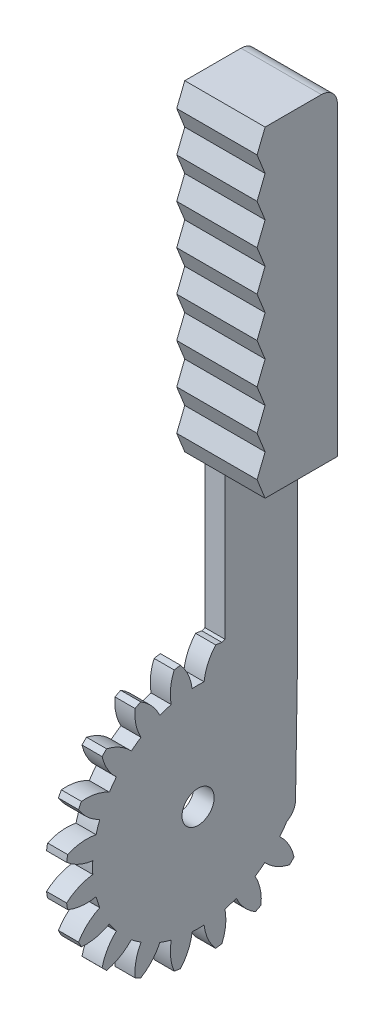
SolidWorks part; units mm, degrees
ref_plane "Plane1" through (0, 0, 0) normal (0, 0, 1) x (1, 0, 0)
ref_plane "Plane2" through (0, 0, 0) normal (0, 1, 0) x (1, 0, 0)
ref_plane "Plane3" through (0, 0, 0) normal (1, 0, 0) x (0, 0, -1)
other "Configuration Table"
sketch "HoldingSke" plane through (0, 0, 0) normal (0, 1, 0) x (1, 0, 0)
  line L0 (0, 0) -> (0.6265, -0.228)
  line L1 (-15, 0) -> (100, 0) construction
  line L2 (0, 0) -> (-2.1039, 2.3779)
  line L3 (0, 0) -> (-11.863, 4.5341)
  line L4 (0, 0) -> (8.1152, 2.9537)
  line L5 (0, 0) -> (-46.8476, -17.4728)
  line L6 (0, 0) -> (-2.0724, -1.3983)
  line L7 (-2.1039, 2.3779) -> (8.6586, 51.2059)
  line L8 (-76.2, 54.61) -> (-75.5, 54.61)
  line L9 (-71.009, 38.7566) -> (-53.1078, 45.2721)
  line L10 (-76.2, 71.12) -> (104.1128, 71.12)
  line L11 (0, 0) -> (-2.5, 0)
  line L12 (-76.2, 101.6) -> (-76.147, 101.6)
  line L13 (24.9733, 27.94) -> (52.9518, 28.4284)
  line L14 (24.9733, 27.94) -> (24.9743, 27.94)
  line L15 (24.9733, 27.94) -> (100.4006, 29.5858)
  line L16 (-63.627, -1.5) -> (-12.827, -1.5)
  circle A0 centre (0, 0) radius 2
  circle A1 centre (0, 0) radius 13.124
  circle A2 centre (0, 0) radius 37.5
  circle A3 centre (0, 0) radius 2
  dimension "Num_teeth" = 20
  dimension "Pitch_radius" = 180.3128
  dimension "Width" = 2.5
  dimension "Thickness" = 2.5
sketch "BasProSke" plane through (0, 0, 0) normal (0, 1, 0) x (1, 0, 0)
  line L0 (-10, 0) -> (60, 0) construction
  line L1 (0, 0) -> (0, 16.5)
  line L2 (0, 0) -> (2.5, 0)
  line L3 (2.5, 0) -> (2.5, 16.5)
  line L4 (2.5, 16.5) -> (0, 16.5)
  dimension "Thickness" = 2.5
  dimension "Diameter" = 33
revolve "Base-Revolve" add sketch "BasProSke" angle 360 about L0
sketch "TooCutSke" plane through (0, 0, 0) normal (1, 0, 0) x (0, 0, -1)
  line L1 (0, 0) -> (0, 107) construction
  line L2 (0, 0) -> (-1.2696, 14.9462) construction
  line L3 (0, 0) -> (-4.6808, 29.5532) construction
  line L4 (-1.2696, 14.9462) -> (-2.3404, 14.7766) construction
  arc A0 (0.7438, 13.1029) -> (-0.7438, 13.1029) centre (0, 0) ccw
  arc A1 (2.21, 16.377) -> (-2.21, 16.377) centre (0, 0) ccw
  circle A2 centre (0, 0) radius 15 construction
  circle A3 centre (0, 0) radius 14.0954 construction
  arc A4 (-0.7438, 13.1029) -> (-2.21, 16.377) centre (-6.7025, 12.3999) ccw
  arc A5 (2.21, 16.377) -> (0.7438, 13.1029) centre (6.7025, 12.3999) ccw
extrude "ToothCut" cut sketch "TooCutSke" along normal through all
fillet "Breaks" [suppressed] radius 0.03 tangent propagation no
fillet "RootFillets" [suppressed] radius 0.376
pattern_circular "TeethCuts" count 20 every 18 about axis through (-10, 0, 0) along (1, 0, 0) of "ToothCut", "RootFillets", "Breaks"
sketch "HubNeaOneSke" plane through (0, 0, 0) normal (-1, 0, 0) x (0, 0, 1)
  circle A0 centre (0, 0) radius 13.124
  dimension "Diameter" = 26.248
extrude "HubNearOne" [suppressed] add sketch "HubNeaOneSke" along normal blind 47.5001
sketch "HubNeaBotSke" plane through (0, 0, 0) normal (-1, 0, 0) x (0, 0, 1)
  circle A0 centre (0, 0) radius 13.124
  dimension "Diameter" = 26.248
extrude "HubNearBoth" [suppressed] add sketch "HubNeaBotSke" along normal blind 23.75
ref_plane "FarPln" through (2.5, 0, 0) normal (1, 0, 0) x (0, 0, -1)
sketch "HubFarSke" plane through (2.5, 0, 0) normal (1, 0, 0) x (0, 0, -1)
  circle A0 centre (0, 0) radius 13.124
  dimension "Diameter" = 26.248
extrude "HubFar" [suppressed] add sketch "HubFarSke" along normal blind 23.75
sketch "BorSke" plane through (0, 0, 0) normal (1, 0, 0) x (0, 0, -1)
  circle A0 centre (0, 0) radius 2
  dimension "Diameter" = 4
extrude "Bore" cut sketch "BorSke" along normal mid plane 100.0001
sketch "KeySke" plane through (0, 0, 0) normal (1, 0, 0) x (0, 0, -1)
  line L0 (-0.8, 0) -> (-0.8, 2.7)
  line L1 (-0.8, 2.7) -> (0.8, 2.7)
  line L2 (0.8, 2.7) -> (0.8, 0)
  line L3 (0, 0) -> (0, 34) construction
  line L4 (-0.8, 0) -> (0.8, 0)
  dimension "Width" = 1.6
extrude "Keyway" [suppressed] cut sketch "KeySke" along normal mid plane 100.0001
pattern_circular "Keyway2" [suppressed] count 2 every 90 about axis through (-10, 0, 0) along (1, 0, 0)
sketch "Sketch1" plane through (2.5, 0, 0) normal (1, 0, 0) x (0, 0, -1)
  line L1 (12.3416, 4.0811) -> (3.3416, 4.0811)
  line L2 (12.3416, 4.0811) -> (12.3416, 74.0811)
  line L3 (12.3416, 74.0811) -> (3.3416, 74.0811)
  line L4 (3.3416, 4.0811) -> (3.3416, 74.0811)
  dimension "D1" = 9
  dimension "D2" = 70
extrude "Boss-Extrude2" add sketch "Sketch1" against normal up to surface (2.5 mm away) up to face at (0, 0, -2)
sketch "Sketch2" plane through (2.5, 0, 0) normal (1, 0, 0) x (0, 0, -1)
  line L3 (3.3416, 74.0811) -> (2.3416, 71.5811)
  line L4 (2.3416, 71.5811) -> (3.3416, 69.0811)
  line L5 (3.3416, 74.0811) -> (3.3416, 15.0369) construction
  line L6 (3.3416, 69.0811) -> (3.3416, 74.0811)
  line L7 (12.3416, 4.4636) -> (12.3416, 4.8084)
  line L8 (12.3416, 7.6405) -> (12.3416, 74.0811)
  line L9 (12.3416, 74.0811) -> (3.3416, 74.0811)
  line L10 (3.3416, 74.0811) -> (3.3416, 15.0369)
  line L11 (12.3416, 4.4636) -> (12.3416, 4.8084)
  line L12 (12.3416, 7.6405) -> (12.3416, 74.0811)
  line L13 (12.3416, 74.0811) -> (3.3416, 74.0811)
  arc A71 (12.6915, 3.3416) -> (12.3416, 4.4636) centre (0, 0) ccw
  arc A72 (12.3416, 4.8084) -> (14.8769, 7.1363) centre (9.7218, 10.2062) ccw
  arc A73 (14.8769, 7.1363) -> (14.5178, 7.8411) centre (0, 0) ccw
  arc A74 (14.5178, 7.8411) -> (12.3416, 7.6405) centre (13.9713, 1.866) ccw
  arc A75 (3.3416, 15.0369) -> (2.9711, 16.2303) centre (-2.5427, 13.8642) ccw
  arc A76 (2.9711, 16.2303) -> (2.1898, 16.354) centre (0, 0) ccw
  arc A77 (2.1898, 16.354) -> (0.7438, 13.1029) centre (6.7025, 12.3999) ccw
  arc A78 (0.7438, 13.1029) -> (-0.7438, 13.1029) centre (0, 0) ccw
  arc A79 (-0.7438, 13.1029) -> (-2.1898, 16.354) centre (-6.7025, 12.3999) ccw
  arc A80 (-2.1898, 16.354) -> (-2.9711, 16.2303) centre (0, 0) ccw
  arc A81 (-2.9711, 16.2303) -> (-3.3416, 12.6915) centre (2.5427, 13.8642) ccw
  arc A82 (-3.3416, 12.6915) -> (-4.7564, 12.2318) centre (0, 0) ccw
  arc A83 (-4.7564, 12.2318) -> (-7.1363, 14.8769) centre (-10.2062, 9.7218) ccw
  arc A84 (-7.1363, 14.8769) -> (-7.8411, 14.5178) centre (0, 0) ccw
  arc A85 (-7.8411, 14.5178) -> (-7.0999, 11.0377) centre (-1.866, 13.9713) ccw
  arc A86 (-7.0999, 11.0377) -> (-8.3035, 10.1633) centre (0, 0) ccw
  arc A87 (-8.3035, 10.1633) -> (-11.3842, 11.9436) centre (-12.7109, 6.0921) ccw
  arc A88 (-11.3842, 11.9436) -> (-11.9436, 11.3842) centre (0, 0) ccw
  arc A89 (-11.9436, 11.3842) -> (-10.1633, 8.3035) centre (-6.0921, 12.7109) ccw
  arc A90 (-10.1633, 8.3035) -> (-11.0377, 7.0999) centre (0, 0) ccw
  arc A91 (-11.0377, 7.0999) -> (-14.5178, 7.8411) centre (-13.9713, 1.866) ccw
  arc A92 (-14.5178, 7.8411) -> (-14.8769, 7.1363) centre (0, 0) ccw
  arc A93 (-14.8769, 7.1363) -> (-12.2318, 4.7564) centre (-9.7218, 10.2062) ccw
  arc A94 (-12.2318, 4.7564) -> (-12.6915, 3.3416) centre (0, 0) ccw
  arc A95 (-12.6915, 3.3416) -> (-16.2303, 2.9711) centre (-13.8642, -2.5427) ccw
  arc A96 (-16.2303, 2.9711) -> (-16.354, 2.1898) centre (0, 0) ccw
  arc A97 (-16.354, 2.1898) -> (-13.1029, 0.7438) centre (-12.3999, 6.7025) ccw
  arc A98 (-13.1029, 0.7438) -> (-13.1029, -0.7438) centre (0, 0) ccw
  arc A99 (-13.1029, -0.7438) -> (-16.354, -2.1898) centre (-12.3999, -6.7025) ccw
  arc A100 (-16.354, -2.1898) -> (-16.2303, -2.9711) centre (0, 0) ccw
  arc A101 (-16.2303, -2.9711) -> (-12.6915, -3.3416) centre (-13.8642, 2.5427) ccw
  arc A102 (-12.6915, -3.3416) -> (-12.2318, -4.7564) centre (0, 0) ccw
  arc A103 (-12.2318, -4.7564) -> (-14.8769, -7.1363) centre (-9.7218, -10.2062) ccw
  arc A104 (-14.8769, -7.1363) -> (-14.5178, -7.8411) centre (0, 0) ccw
  arc A105 (-14.5178, -7.8411) -> (-11.0377, -7.0999) centre (-13.9713, -1.866) ccw
  arc A106 (-11.0377, -7.0999) -> (-10.1633, -8.3035) centre (0, 0) ccw
  arc A107 (-10.1633, -8.3035) -> (-11.9436, -11.3842) centre (-6.0921, -12.7109) ccw
  arc A108 (-11.9436, -11.3842) -> (-11.3842, -11.9436) centre (0, 0) ccw
  arc A109 (-11.3842, -11.9436) -> (-8.3035, -10.1633) centre (-12.7109, -6.0921) ccw
  arc A110 (-8.3035, -10.1633) -> (-7.0999, -11.0377) centre (0, 0) ccw
  arc A111 (-7.0999, -11.0377) -> (-7.8411, -14.5178) centre (-1.866, -13.9713) ccw
  arc A112 (-7.8411, -14.5178) -> (-7.1363, -14.8769) centre (0, 0) ccw
  arc A113 (-7.1363, -14.8769) -> (-4.7564, -12.2318) centre (-10.2062, -9.7218) ccw
  arc A114 (-4.7564, -12.2318) -> (-3.3416, -12.6915) centre (0, 0) ccw
  arc A115 (-3.3416, -12.6915) -> (-2.9711, -16.2303) centre (2.5427, -13.8642) ccw
  arc A116 (-2.9711, -16.2303) -> (-2.1898, -16.354) centre (0, 0) ccw
  arc A117 (-2.1898, -16.354) -> (-0.7438, -13.1029) centre (-6.7025, -12.3999) ccw
  arc A118 (-0.7438, -13.1029) -> (0.7438, -13.1029) centre (0, 0) ccw
  arc A119 (0.7438, -13.1029) -> (2.1898, -16.354) centre (6.7025, -12.3999) ccw
  arc A120 (2.1898, -16.354) -> (2.9711, -16.2303) centre (0, 0) ccw
  arc A121 (2.9711, -16.2303) -> (3.3416, -12.6915) centre (-2.5427, -13.8642) ccw
  arc A122 (3.3416, -12.6915) -> (4.7564, -12.2318) centre (0, 0) ccw
  arc A123 (4.7564, -12.2318) -> (7.1363, -14.8769) centre (10.2062, -9.7218) ccw
  arc A124 (7.1363, -14.8769) -> (7.8411, -14.5178) centre (0, 0) ccw
  arc A125 (7.8411, -14.5178) -> (7.0999, -11.0377) centre (1.866, -13.9713) ccw
  arc A126 (7.0999, -11.0377) -> (8.3035, -10.1633) centre (0, 0) ccw
  arc A127 (8.3035, -10.1633) -> (11.3842, -11.9436) centre (12.7109, -6.0921) ccw
  arc A128 (11.3842, -11.9436) -> (11.9436, -11.3842) centre (0, 0) ccw
  arc A129 (11.9436, -11.3842) -> (10.1633, -8.3035) centre (6.0921, -12.7109) ccw
  arc A130 (10.1633, -8.3035) -> (11.0377, -7.0999) centre (0, 0) ccw
  arc A131 (11.0377, -7.0999) -> (14.5178, -7.8411) centre (13.9713, -1.866) ccw
  arc A132 (14.5178, -7.8411) -> (14.8769, -7.1363) centre (0, 0) ccw
  arc A133 (14.8769, -7.1363) -> (12.2318, -4.7564) centre (9.7218, -10.2062) ccw
  arc A134 (12.2318, -4.7564) -> (12.6915, -3.3416) centre (0, 0) ccw
  arc A135 (12.6915, -3.3416) -> (16.2303, -2.9711) centre (13.8642, 2.5427) ccw
  arc A136 (16.2303, -2.9711) -> (16.354, -2.1898) centre (0, 0) ccw
  arc A137 (16.354, -2.1898) -> (13.1029, -0.7438) centre (12.3999, -6.7025) ccw
  arc A138 (13.1029, -0.7438) -> (13.1029, 0.7438) centre (0, 0) ccw
  arc A139 (13.1029, 0.7438) -> (16.354, 2.1898) centre (12.3999, 6.7025) ccw
  arc A140 (16.354, 2.1898) -> (16.2303, 2.9711) centre (0, 0) ccw
  arc A141 (16.2303, 2.9711) -> (12.6915, 3.3416) centre (13.8642, -2.5427) ccw
  arc A142 (12.6915, 3.3416) -> (12.3416, 4.4636) centre (0, 0) ccw
  arc A143 (12.3416, 4.8084) -> (14.8769, 7.1363) centre (9.7218, 10.2062) ccw
  arc A144 (14.8769, 7.1363) -> (14.5178, 7.8411) centre (0, 0) ccw
  arc A145 (14.5178, 7.8411) -> (12.3416, 7.6405) centre (13.9713, 1.866) ccw
  arc A146 (3.3416, 15.0369) -> (2.9711, 16.2303) centre (-2.5427, 13.8642) ccw
  arc A147 (2.9711, 16.2303) -> (2.1898, 16.354) centre (0, 0) ccw
  arc A148 (2.1898, 16.354) -> (0.7438, 13.1029) centre (6.7025, 12.3999) ccw
  arc A149 (0.7438, 13.1029) -> (-0.7438, 13.1029) centre (0, 0) ccw
  arc A150 (-0.7438, 13.1029) -> (-2.1898, 16.354) centre (-6.7025, 12.3999) ccw
  arc A151 (-2.1898, 16.354) -> (-2.9711, 16.2303) centre (0, 0) ccw
  arc A152 (-2.9711, 16.2303) -> (-3.3416, 12.6915) centre (2.5427, 13.8642) ccw
  arc A153 (-3.3416, 12.6915) -> (-4.7564, 12.2318) centre (0, 0) ccw
  arc A154 (-4.7564, 12.2318) -> (-7.1363, 14.8769) centre (-10.2062, 9.7218) ccw
  arc A155 (-7.1363, 14.8769) -> (-7.8411, 14.5178) centre (0, 0) ccw
  arc A156 (-7.8411, 14.5178) -> (-7.0999, 11.0377) centre (-1.866, 13.9713) ccw
  arc A157 (-7.0999, 11.0377) -> (-8.3035, 10.1633) centre (0, 0) ccw
  arc A158 (-8.3035, 10.1633) -> (-11.3842, 11.9436) centre (-12.7109, 6.0921) ccw
  arc A159 (-11.3842, 11.9436) -> (-11.9436, 11.3842) centre (0, 0) ccw
  arc A160 (-11.9436, 11.3842) -> (-10.1633, 8.3035) centre (-6.0921, 12.7109) ccw
  arc A161 (-10.1633, 8.3035) -> (-11.0377, 7.0999) centre (0, 0) ccw
  arc A162 (-11.0377, 7.0999) -> (-14.5178, 7.8411) centre (-13.9713, 1.866) ccw
  arc A163 (-14.5178, 7.8411) -> (-14.8769, 7.1363) centre (0, 0) ccw
  arc A164 (-14.8769, 7.1363) -> (-12.2318, 4.7564) centre (-9.7218, 10.2062) ccw
  arc A165 (-12.2318, 4.7564) -> (-12.6915, 3.3416) centre (0, 0) ccw
  arc A166 (-12.6915, 3.3416) -> (-16.2303, 2.9711) centre (-13.8642, -2.5427) ccw
  arc A167 (-16.2303, 2.9711) -> (-16.354, 2.1898) centre (0, 0) ccw
  arc A168 (-16.354, 2.1898) -> (-13.1029, 0.7438) centre (-12.3999, 6.7025) ccw
  arc A169 (-13.1029, 0.7438) -> (-13.1029, -0.7438) centre (0, 0) ccw
  arc A170 (-13.1029, -0.7438) -> (-16.354, -2.1898) centre (-12.3999, -6.7025) ccw
  arc A171 (-16.354, -2.1898) -> (-16.2303, -2.9711) centre (0, 0) ccw
  arc A172 (-16.2303, -2.9711) -> (-12.6915, -3.3416) centre (-13.8642, 2.5427) ccw
  arc A173 (-12.6915, -3.3416) -> (-12.2318, -4.7564) centre (0, 0) ccw
  arc A174 (-12.2318, -4.7564) -> (-14.8769, -7.1363) centre (-9.7218, -10.2062) ccw
  arc A175 (-14.8769, -7.1363) -> (-14.5178, -7.8411) centre (0, 0) ccw
  arc A176 (-14.5178, -7.8411) -> (-11.0377, -7.0999) centre (-13.9713, -1.866) ccw
  arc A177 (-11.0377, -7.0999) -> (-10.1633, -8.3035) centre (0, 0) ccw
  arc A178 (-10.1633, -8.3035) -> (-11.9436, -11.3842) centre (-6.0921, -12.7109) ccw
  arc A179 (-11.9436, -11.3842) -> (-11.3842, -11.9436) centre (0, 0) ccw
  arc A180 (-11.3842, -11.9436) -> (-8.3035, -10.1633) centre (-12.7109, -6.0921) ccw
  arc A181 (-8.3035, -10.1633) -> (-7.0999, -11.0377) centre (0, 0) ccw
  arc A182 (-7.0999, -11.0377) -> (-7.8411, -14.5178) centre (-1.866, -13.9713) ccw
  arc A183 (-7.8411, -14.5178) -> (-7.1363, -14.8769) centre (0, 0) ccw
  arc A184 (-7.1363, -14.8769) -> (-4.7564, -12.2318) centre (-10.2062, -9.7218) ccw
  arc A185 (-4.7564, -12.2318) -> (-3.3416, -12.6915) centre (0, 0) ccw
  arc A186 (-3.3416, -12.6915) -> (-2.9711, -16.2303) centre (2.5427, -13.8642) ccw
  arc A187 (-2.9711, -16.2303) -> (-2.1898, -16.354) centre (0, 0) ccw
  arc A188 (-2.1898, -16.354) -> (-0.7438, -13.1029) centre (-6.7025, -12.3999) ccw
  arc A189 (-0.7438, -13.1029) -> (0.7438, -13.1029) centre (0, 0) ccw
  arc A190 (0.7438, -13.1029) -> (2.1898, -16.354) centre (6.7025, -12.3999) ccw
  arc A191 (2.1898, -16.354) -> (2.9711, -16.2303) centre (0, 0) ccw
  arc A192 (2.9711, -16.2303) -> (3.3416, -12.6915) centre (-2.5427, -13.8642) ccw
  arc A193 (3.3416, -12.6915) -> (4.7564, -12.2318) centre (0, 0) ccw
  arc A194 (4.7564, -12.2318) -> (7.1363, -14.8769) centre (10.2062, -9.7218) ccw
  arc A195 (7.1363, -14.8769) -> (7.8411, -14.5178) centre (0, 0) ccw
  arc A196 (7.8411, -14.5178) -> (7.0999, -11.0377) centre (1.866, -13.9713) ccw
  arc A197 (7.0999, -11.0377) -> (8.3035, -10.1633) centre (0, 0) ccw
  arc A198 (8.3035, -10.1633) -> (11.3842, -11.9436) centre (12.7109, -6.0921) ccw
  arc A199 (11.3842, -11.9436) -> (11.9436, -11.3842) centre (0, 0) ccw
  arc A200 (11.9436, -11.3842) -> (10.1633, -8.3035) centre (6.0921, -12.7109) ccw
  arc A201 (10.1633, -8.3035) -> (11.0377, -7.0999) centre (0, 0) ccw
  arc A202 (11.0377, -7.0999) -> (14.5178, -7.8411) centre (13.9713, -1.866) ccw
  arc A203 (14.5178, -7.8411) -> (14.8769, -7.1363) centre (0, 0) ccw
  arc A204 (14.8769, -7.1363) -> (12.2318, -4.7564) centre (9.7218, -10.2062) ccw
  arc A205 (12.2318, -4.7564) -> (12.6915, -3.3416) centre (0, 0) ccw
  arc A206 (12.6915, -3.3416) -> (16.2303, -2.9711) centre (13.8642, 2.5427) ccw
  arc A207 (16.2303, -2.9711) -> (16.354, -2.1898) centre (0, 0) ccw
  arc A208 (16.354, -2.1898) -> (13.1029, -0.7438) centre (12.3999, -6.7025) ccw
  arc A209 (13.1029, -0.7438) -> (13.1029, 0.7438) centre (0, 0) ccw
  arc A210 (13.1029, 0.7438) -> (16.354, 2.1898) centre (12.3999, 6.7025) ccw
  arc A211 (16.354, 2.1898) -> (16.2303, 2.9711) centre (0, 0) ccw
  arc A212 (16.2303, 2.9711) -> (12.6915, 3.3416) centre (13.8642, -2.5427) ccw
  dimension "D1" = 5
  dimension "D2" = 1
  dimension "D3" = 0
extrude "Boss-Extrude3" add sketch "Sketch2" against normal up to surface (2.5 mm away) contours L4 L6 L3 region at (2.5, 71.5811, -3.0083) up to face at (0, 0.8087, 0.528)
pattern_linear "LPattern2" count 8 spacing 5 along (0, -1, 0) of "Boss-Extrude3"
sketch "Sketch3" plane through (2.5, 0, 0) normal (1, 0, 0) x (0, 0, -1)
  line L0 (12.3416, 7.6405) -> (11.9436, -16.474)
  line L1 (11.9436, -16.474) -> (28.1206, -19.0025)
  line L2 (28.1206, -19.0025) -> (23.7943, 10.9484)
  line L3 (23.7943, 10.9484) -> (12.3416, 7.6405)
extrude "Cut-Extrude1" cut sketch "Sketch3" against normal blind 3
fillet "Fillet3" radius 2 1 edges at (1.25, -7.5637, -12.0907)
fillet "Fillet4" radius 2 1 edges at (1.25, 74.0811, -12.3416)
sketch "Sketch5" plane through (2.5, 0, 0) normal (1, 0, 0) x (0, 0, -1)
  line L0 (2.9711, 16.2303) -> (3.3416, 16.3893)
  line L1 (3.3416, 16.3893) -> (3.3416, 15.0369)
  line L2 (2.9711, 16.2303) -> (3.3416, 15.0369)
  line L20 (12.3416, 7.6405) -> (12.3416, 72.0811)
  line L21 (10.3416, 74.0811) -> (3.3416, 74.0811)
  line L22 (3.3416, 74.0811) -> (2.3416, 71.5811)
  line L23 (2.3416, 71.5811) -> (3.3416, 69.0811)
  line L24 (3.3416, 69.0811) -> (2.3416, 66.5811)
  line L25 (2.3416, 66.5811) -> (3.3416, 64.0811)
  line L26 (3.3416, 64.0811) -> (2.3416, 61.5811)
  line L27 (2.3416, 61.5811) -> (3.3416, 59.0811)
  line L28 (3.3416, 59.0811) -> (2.3416, 56.5811)
  line L29 (2.3416, 56.5811) -> (3.3416, 54.0811)
  line L30 (3.3416, 54.0811) -> (2.3416, 51.5811)
  line L31 (2.3416, 51.5811) -> (3.3416, 49.0811)
  line L32 (3.3416, 49.0811) -> (2.3416, 46.5811)
  line L33 (2.3416, 46.5811) -> (3.3416, 44.0811)
  line L34 (3.3416, 44.0811) -> (2.3416, 41.5811)
  line L35 (2.3416, 41.5811) -> (3.3416, 39.0811)
  line L36 (3.3416, 39.0811) -> (2.3416, 36.5811)
  line L37 (2.3416, 36.5811) -> (3.3416, 34.0811)
  line L38 (3.3416, 34.0811) -> (3.3416, 15.0369)
  line L39 (12.1272, -5.3521) -> (12.3416, 7.6405)
  line L40 (12.3416, 7.6405) -> (12.3416, 72.0811)
  line L41 (10.3416, 74.0811) -> (3.3416, 74.0811)
  line L42 (3.3416, 74.0811) -> (2.3416, 71.5811)
  line L43 (2.3416, 71.5811) -> (3.3416, 69.0811)
  line L44 (3.3416, 69.0811) -> (2.3416, 66.5811)
  line L45 (2.3416, 66.5811) -> (3.3416, 64.0811)
  line L46 (3.3416, 64.0811) -> (2.3416, 61.5811)
  line L47 (2.3416, 61.5811) -> (3.3416, 59.0811)
  line L48 (3.3416, 59.0811) -> (2.3416, 56.5811)
  line L49 (2.3416, 56.5811) -> (3.3416, 54.0811)
  line L50 (3.3416, 54.0811) -> (2.3416, 51.5811)
  line L51 (2.3416, 51.5811) -> (3.3416, 49.0811)
  line L52 (3.3416, 49.0811) -> (2.3416, 46.5811)
  line L53 (2.3416, 46.5811) -> (3.3416, 44.0811)
  line L54 (3.3416, 44.0811) -> (2.3416, 41.5811)
  line L55 (2.3416, 41.5811) -> (3.3416, 39.0811)
  line L56 (3.3416, 39.0811) -> (2.3416, 36.5811)
  line L57 (2.3416, 36.5811) -> (3.3416, 34.0811)
  line L58 (3.3416, 34.0811) -> (3.3416, 15.0369)
  line L59 (12.1272, -5.3521) -> (12.3416, 7.6405)
  arc A58 (12.3416, 72.0811) -> (10.3416, 74.0811) centre (10.3416, 72.0811) ccw
  arc A59 (3.3416, 15.0369) -> (2.9711, 16.2303) centre (-2.5427, 13.8642) ccw
  arc A60 (2.9711, 16.2303) -> (2.1898, 16.354) centre (0, 0) ccw
  arc A61 (2.1898, 16.354) -> (0.7438, 13.1029) centre (6.7025, 12.3999) ccw
  arc A62 (0.7438, 13.1029) -> (-0.7438, 13.1029) centre (0, 0) ccw
  arc A63 (-0.7438, 13.1029) -> (-2.1898, 16.354) centre (-6.7025, 12.3999) ccw
  arc A64 (-2.1898, 16.354) -> (-2.9711, 16.2303) centre (0, 0) ccw
  arc A65 (-2.9711, 16.2303) -> (-3.3416, 12.6915) centre (2.5427, 13.8642) ccw
  arc A66 (-3.3416, 12.6915) -> (-4.7564, 12.2318) centre (0, 0) ccw
  arc A67 (-4.7564, 12.2318) -> (-7.1363, 14.8769) centre (-10.2062, 9.7218) ccw
  arc A68 (-7.1363, 14.8769) -> (-7.8411, 14.5178) centre (0, 0) ccw
  arc A69 (-7.8411, 14.5178) -> (-7.0999, 11.0377) centre (-1.866, 13.9713) ccw
  arc A70 (-7.0999, 11.0377) -> (-8.3035, 10.1633) centre (0, 0) ccw
  arc A71 (-8.3035, 10.1633) -> (-11.3842, 11.9436) centre (-12.7109, 6.0921) ccw
  arc A72 (-11.3842, 11.9436) -> (-11.9436, 11.3842) centre (0, 0) ccw
  arc A73 (-11.9436, 11.3842) -> (-10.1633, 8.3035) centre (-6.0921, 12.7109) ccw
  arc A74 (-10.1633, 8.3035) -> (-11.0377, 7.0999) centre (0, 0) ccw
  arc A75 (-11.0377, 7.0999) -> (-14.5178, 7.8411) centre (-13.9713, 1.866) ccw
  arc A76 (-14.5178, 7.8411) -> (-14.8769, 7.1363) centre (0, 0) ccw
  arc A77 (-14.8769, 7.1363) -> (-12.2318, 4.7564) centre (-9.7218, 10.2062) ccw
  arc A78 (-12.2318, 4.7564) -> (-12.6915, 3.3416) centre (0, 0) ccw
  arc A79 (-12.6915, 3.3416) -> (-16.2303, 2.9711) centre (-13.8642, -2.5427) ccw
  arc A80 (-16.2303, 2.9711) -> (-16.354, 2.1898) centre (0, 0) ccw
  arc A81 (-16.354, 2.1898) -> (-13.1029, 0.7438) centre (-12.3999, 6.7025) ccw
  arc A82 (-13.1029, 0.7438) -> (-13.1029, -0.7438) centre (0, 0) ccw
  arc A83 (-13.1029, -0.7438) -> (-16.354, -2.1898) centre (-12.3999, -6.7025) ccw
  arc A84 (-16.354, -2.1898) -> (-16.2303, -2.9711) centre (0, 0) ccw
  arc A85 (-16.2303, -2.9711) -> (-12.6915, -3.3416) centre (-13.8642, 2.5427) ccw
  arc A86 (-12.6915, -3.3416) -> (-12.2318, -4.7564) centre (0, 0) ccw
  arc A87 (-12.2318, -4.7564) -> (-14.8769, -7.1363) centre (-9.7218, -10.2062) ccw
  arc A88 (-14.8769, -7.1363) -> (-14.5178, -7.8411) centre (0, 0) ccw
  arc A89 (-14.5178, -7.8411) -> (-11.0377, -7.0999) centre (-13.9713, -1.866) ccw
  arc A90 (-11.0377, -7.0999) -> (-10.1633, -8.3035) centre (0, 0) ccw
  arc A91 (-10.1633, -8.3035) -> (-11.9436, -11.3842) centre (-6.0921, -12.7109) ccw
  arc A92 (-11.9436, -11.3842) -> (-11.3842, -11.9436) centre (0, 0) ccw
  arc A93 (-11.3842, -11.9436) -> (-8.3035, -10.1633) centre (-12.7109, -6.0921) ccw
  arc A94 (-8.3035, -10.1633) -> (-7.0999, -11.0377) centre (0, 0) ccw
  arc A95 (-7.0999, -11.0377) -> (-7.8411, -14.5178) centre (-1.866, -13.9713) ccw
  arc A96 (-7.8411, -14.5178) -> (-7.1363, -14.8769) centre (0, 0) ccw
  arc A97 (-7.1363, -14.8769) -> (-4.7564, -12.2318) centre (-10.2062, -9.7218) ccw
  arc A98 (-4.7564, -12.2318) -> (-3.3416, -12.6915) centre (0, 0) ccw
  arc A99 (-3.3416, -12.6915) -> (-2.9711, -16.2303) centre (2.5427, -13.8642) ccw
  arc A100 (-2.9711, -16.2303) -> (-2.1898, -16.354) centre (0, 0) ccw
  arc A101 (-2.1898, -16.354) -> (-0.7438, -13.1029) centre (-6.7025, -12.3999) ccw
  arc A102 (-0.7438, -13.1029) -> (0.7438, -13.1029) centre (0, 0) ccw
  arc A103 (0.7438, -13.1029) -> (2.1898, -16.354) centre (6.7025, -12.3999) ccw
  arc A104 (2.1898, -16.354) -> (2.9711, -16.2303) centre (0, 0) ccw
  arc A105 (2.9711, -16.2303) -> (3.3416, -12.6915) centre (-2.5427, -13.8642) ccw
  arc A106 (3.3416, -12.6915) -> (4.7564, -12.2318) centre (0, 0) ccw
  arc A107 (4.7564, -12.2318) -> (7.1363, -14.8769) centre (10.2062, -9.7218) ccw
  arc A108 (7.1363, -14.8769) -> (7.8411, -14.5178) centre (0, 0) ccw
  arc A109 (7.8411, -14.5178) -> (7.0999, -11.0377) centre (1.866, -13.9713) ccw
  arc A110 (7.0999, -11.0377) -> (8.3035, -10.1633) centre (0, 0) ccw
  arc A111 (8.3035, -10.1633) -> (11.3842, -11.9436) centre (12.7109, -6.0921) ccw
  arc A112 (11.3842, -11.9436) -> (11.9436, -11.3842) centre (0, 0) ccw
  arc A113 (11.9436, -11.3842) -> (10.1633, -8.3035) centre (6.0921, -12.7109) ccw
  arc A114 (10.1633, -8.3035) -> (11.0377, -7.0999) centre (0, 0) ccw
  arc A115 (11.0377, -7.0999) -> (12.1272, -5.3521) centre (10.1274, -5.3191) ccw
  arc A116 (12.3416, 72.0811) -> (10.3416, 74.0811) centre (10.3416, 72.0811) ccw
  arc A117 (3.3416, 15.0369) -> (2.9711, 16.2303) centre (-2.5427, 13.8642) ccw
  arc A118 (2.9711, 16.2303) -> (2.1898, 16.354) centre (0, 0) ccw
  arc A119 (2.1898, 16.354) -> (0.7438, 13.1029) centre (6.7025, 12.3999) ccw
  arc A120 (0.7438, 13.1029) -> (-0.7438, 13.1029) centre (0, 0) ccw
  arc A121 (-0.7438, 13.1029) -> (-2.1898, 16.354) centre (-6.7025, 12.3999) ccw
  arc A122 (-2.1898, 16.354) -> (-2.9711, 16.2303) centre (0, 0) ccw
  arc A123 (-2.9711, 16.2303) -> (-3.3416, 12.6915) centre (2.5427, 13.8642) ccw
  arc A124 (-3.3416, 12.6915) -> (-4.7564, 12.2318) centre (0, 0) ccw
  arc A125 (-4.7564, 12.2318) -> (-7.1363, 14.8769) centre (-10.2062, 9.7218) ccw
  arc A126 (-7.1363, 14.8769) -> (-7.8411, 14.5178) centre (0, 0) ccw
  arc A127 (-7.8411, 14.5178) -> (-7.0999, 11.0377) centre (-1.866, 13.9713) ccw
  arc A128 (-7.0999, 11.0377) -> (-8.3035, 10.1633) centre (0, 0) ccw
  arc A129 (-8.3035, 10.1633) -> (-11.3842, 11.9436) centre (-12.7109, 6.0921) ccw
  arc A130 (-11.3842, 11.9436) -> (-11.9436, 11.3842) centre (0, 0) ccw
  arc A131 (-11.9436, 11.3842) -> (-10.1633, 8.3035) centre (-6.0921, 12.7109) ccw
  arc A132 (-10.1633, 8.3035) -> (-11.0377, 7.0999) centre (0, 0) ccw
  arc A133 (-11.0377, 7.0999) -> (-14.5178, 7.8411) centre (-13.9713, 1.866) ccw
  arc A134 (-14.5178, 7.8411) -> (-14.8769, 7.1363) centre (0, 0) ccw
  arc A135 (-14.8769, 7.1363) -> (-12.2318, 4.7564) centre (-9.7218, 10.2062) ccw
  arc A136 (-12.2318, 4.7564) -> (-12.6915, 3.3416) centre (0, 0) ccw
  arc A137 (-12.6915, 3.3416) -> (-16.2303, 2.9711) centre (-13.8642, -2.5427) ccw
  arc A138 (-16.2303, 2.9711) -> (-16.354, 2.1898) centre (0, 0) ccw
  arc A139 (-16.354, 2.1898) -> (-13.1029, 0.7438) centre (-12.3999, 6.7025) ccw
  arc A140 (-13.1029, 0.7438) -> (-13.1029, -0.7438) centre (0, 0) ccw
  arc A141 (-13.1029, -0.7438) -> (-16.354, -2.1898) centre (-12.3999, -6.7025) ccw
  arc A142 (-16.354, -2.1898) -> (-16.2303, -2.9711) centre (0, 0) ccw
  arc A143 (-16.2303, -2.9711) -> (-12.6915, -3.3416) centre (-13.8642, 2.5427) ccw
  arc A144 (-12.6915, -3.3416) -> (-12.2318, -4.7564) centre (0, 0) ccw
  arc A145 (-12.2318, -4.7564) -> (-14.8769, -7.1363) centre (-9.7218, -10.2062) ccw
  arc A146 (-14.8769, -7.1363) -> (-14.5178, -7.8411) centre (0, 0) ccw
  arc A147 (-14.5178, -7.8411) -> (-11.0377, -7.0999) centre (-13.9713, -1.866) ccw
  arc A148 (-11.0377, -7.0999) -> (-10.1633, -8.3035) centre (0, 0) ccw
  arc A149 (-10.1633, -8.3035) -> (-11.9436, -11.3842) centre (-6.0921, -12.7109) ccw
  arc A150 (-11.9436, -11.3842) -> (-11.3842, -11.9436) centre (0, 0) ccw
  arc A151 (-11.3842, -11.9436) -> (-8.3035, -10.1633) centre (-12.7109, -6.0921) ccw
  arc A152 (-8.3035, -10.1633) -> (-7.0999, -11.0377) centre (0, 0) ccw
  arc A153 (-7.0999, -11.0377) -> (-7.8411, -14.5178) centre (-1.866, -13.9713) ccw
  arc A154 (-7.8411, -14.5178) -> (-7.1363, -14.8769) centre (0, 0) ccw
  arc A155 (-7.1363, -14.8769) -> (-4.7564, -12.2318) centre (-10.2062, -9.7218) ccw
  arc A156 (-4.7564, -12.2318) -> (-3.3416, -12.6915) centre (0, 0) ccw
  arc A157 (-3.3416, -12.6915) -> (-2.9711, -16.2303) centre (2.5427, -13.8642) ccw
  arc A158 (-2.9711, -16.2303) -> (-2.1898, -16.354) centre (0, 0) ccw
  arc A159 (-2.1898, -16.354) -> (-0.7438, -13.1029) centre (-6.7025, -12.3999) ccw
  arc A160 (-0.7438, -13.1029) -> (0.7438, -13.1029) centre (0, 0) ccw
  arc A161 (0.7438, -13.1029) -> (2.1898, -16.354) centre (6.7025, -12.3999) ccw
  arc A162 (2.1898, -16.354) -> (2.9711, -16.2303) centre (0, 0) ccw
  arc A163 (2.9711, -16.2303) -> (3.3416, -12.6915) centre (-2.5427, -13.8642) ccw
  arc A164 (3.3416, -12.6915) -> (4.7564, -12.2318) centre (0, 0) ccw
  arc A165 (4.7564, -12.2318) -> (7.1363, -14.8769) centre (10.2062, -9.7218) ccw
  arc A166 (7.1363, -14.8769) -> (7.8411, -14.5178) centre (0, 0) ccw
  arc A167 (7.8411, -14.5178) -> (7.0999, -11.0377) centre (1.866, -13.9713) ccw
  arc A168 (7.0999, -11.0377) -> (8.3035, -10.1633) centre (0, 0) ccw
  arc A169 (8.3035, -10.1633) -> (11.3842, -11.9436) centre (12.7109, -6.0921) ccw
  arc A170 (11.3842, -11.9436) -> (11.9436, -11.3842) centre (0, 0) ccw
  arc A171 (11.9436, -11.3842) -> (10.1633, -8.3035) centre (6.0921, -12.7109) ccw
  arc A172 (10.1633, -8.3035) -> (11.0377, -7.0999) centre (0, 0) ccw
  arc A173 (11.0377, -7.0999) -> (12.1272, -5.3521) centre (10.1274, -5.3191) ccw
  dimension "D1" = 0
extrude "Boss-Extrude4" add sketch "Sketch5" against normal up to surface (2.5 mm away) contours A117 L1 L0 region at (2.5, 15.9157, -3.2241) up to face at (0, 12.4177, 2.3603)
sketch "Sketch6" plane through (2.5, 0, 0) normal (1, 0, 0) x (0, 0, -1)
  line L0 (12.3416, 34.0811) -> (3.3416, 34.0811)
  line L21 (12.3416, 7.6405) -> (12.3416, 72.0811)
  line L22 (10.3416, 74.0811) -> (3.3416, 74.0811)
  line L23 (3.3416, 74.0811) -> (2.3416, 71.5811)
  line L24 (2.3416, 71.5811) -> (3.3416, 69.0811)
  line L25 (3.3416, 69.0811) -> (2.3416, 66.5811)
  line L26 (2.3416, 66.5811) -> (3.3416, 64.0811)
  line L27 (3.3416, 64.0811) -> (2.3416, 61.5811)
  line L28 (2.3416, 61.5811) -> (3.3416, 59.0811)
  line L29 (3.3416, 59.0811) -> (2.3416, 56.5811)
  line L30 (2.3416, 56.5811) -> (3.3416, 54.0811)
  line L31 (3.3416, 54.0811) -> (2.3416, 51.5811)
  line L32 (2.3416, 51.5811) -> (3.3416, 49.0811)
  line L33 (3.3416, 49.0811) -> (2.3416, 46.5811)
  line L34 (2.3416, 46.5811) -> (3.3416, 44.0811)
  line L35 (3.3416, 44.0811) -> (2.3416, 41.5811)
  line L36 (2.3416, 41.5811) -> (3.3416, 39.0811)
  line L37 (3.3416, 39.0811) -> (2.3416, 36.5811)
  line L38 (2.3416, 36.5811) -> (3.3416, 34.0811)
  line L39 (3.3416, 34.0811) -> (3.3416, 16.3893)
  line L40 (3.3416, 16.3893) -> (2.9711, 16.2303)
  line L41 (12.1272, -5.3521) -> (12.3416, 7.6405)
  line L42 (12.3416, 7.6405) -> (12.3416, 72.0811)
  line L43 (10.3416, 74.0811) -> (3.3416, 74.0811)
  line L44 (3.3416, 74.0811) -> (2.3416, 71.5811)
  line L45 (2.3416, 71.5811) -> (3.3416, 69.0811)
  line L46 (3.3416, 69.0811) -> (2.3416, 66.5811)
  line L47 (2.3416, 66.5811) -> (3.3416, 64.0811)
  line L48 (3.3416, 64.0811) -> (2.3416, 61.5811)
  line L49 (2.3416, 61.5811) -> (3.3416, 59.0811)
  line L50 (3.3416, 59.0811) -> (2.3416, 56.5811)
  line L51 (2.3416, 56.5811) -> (3.3416, 54.0811)
  line L52 (3.3416, 54.0811) -> (2.3416, 51.5811)
  line L53 (2.3416, 51.5811) -> (3.3416, 49.0811)
  line L54 (3.3416, 49.0811) -> (2.3416, 46.5811)
  line L55 (2.3416, 46.5811) -> (3.3416, 44.0811)
  line L56 (3.3416, 44.0811) -> (2.3416, 41.5811)
  line L57 (2.3416, 41.5811) -> (3.3416, 39.0811)
  line L58 (3.3416, 39.0811) -> (2.3416, 36.5811)
  line L59 (2.3416, 36.5811) -> (3.3416, 34.0811)
  line L60 (3.3416, 34.0811) -> (3.3416, 16.3893)
  line L61 (3.3416, 16.3893) -> (2.9711, 16.2303)
  line L62 (12.1272, -5.3521) -> (12.3416, 7.6405)
  arc A57 (12.3416, 72.0811) -> (10.3416, 74.0811) centre (10.3416, 72.0811) ccw
  arc A58 (2.9711, 16.2303) -> (2.1898, 16.354) centre (0, 0) ccw
  arc A59 (2.1898, 16.354) -> (0.7438, 13.1029) centre (6.7025, 12.3999) ccw
  arc A60 (0.7438, 13.1029) -> (-0.7438, 13.1029) centre (0, 0) ccw
  arc A61 (-0.7438, 13.1029) -> (-2.1898, 16.354) centre (-6.7025, 12.3999) ccw
  arc A62 (-2.1898, 16.354) -> (-2.9711, 16.2303) centre (0, 0) ccw
  arc A63 (-2.9711, 16.2303) -> (-3.3416, 12.6915) centre (2.5427, 13.8642) ccw
  arc A64 (-3.3416, 12.6915) -> (-4.7564, 12.2318) centre (0, 0) ccw
  arc A65 (-4.7564, 12.2318) -> (-7.1363, 14.8769) centre (-10.2062, 9.7218) ccw
  arc A66 (-7.1363, 14.8769) -> (-7.8411, 14.5178) centre (0, 0) ccw
  arc A67 (-7.8411, 14.5178) -> (-7.0999, 11.0377) centre (-1.866, 13.9713) ccw
  arc A68 (-7.0999, 11.0377) -> (-8.3035, 10.1633) centre (0, 0) ccw
  arc A69 (-8.3035, 10.1633) -> (-11.3842, 11.9436) centre (-12.7109, 6.0921) ccw
  arc A70 (-11.3842, 11.9436) -> (-11.9436, 11.3842) centre (0, 0) ccw
  arc A71 (-11.9436, 11.3842) -> (-10.1633, 8.3035) centre (-6.0921, 12.7109) ccw
  arc A72 (-10.1633, 8.3035) -> (-11.0377, 7.0999) centre (0, 0) ccw
  arc A73 (-11.0377, 7.0999) -> (-14.5178, 7.8411) centre (-13.9713, 1.866) ccw
  arc A74 (-14.5178, 7.8411) -> (-14.8769, 7.1363) centre (0, 0) ccw
  arc A75 (-14.8769, 7.1363) -> (-12.2318, 4.7564) centre (-9.7218, 10.2062) ccw
  arc A76 (-12.2318, 4.7564) -> (-12.6915, 3.3416) centre (0, 0) ccw
  arc A77 (-12.6915, 3.3416) -> (-16.2303, 2.9711) centre (-13.8642, -2.5427) ccw
  arc A78 (-16.2303, 2.9711) -> (-16.354, 2.1898) centre (0, 0) ccw
  arc A79 (-16.354, 2.1898) -> (-13.1029, 0.7438) centre (-12.3999, 6.7025) ccw
  arc A80 (-13.1029, 0.7438) -> (-13.1029, -0.7438) centre (0, 0) ccw
  arc A81 (-13.1029, -0.7438) -> (-16.354, -2.1898) centre (-12.3999, -6.7025) ccw
  arc A82 (-16.354, -2.1898) -> (-16.2303, -2.9711) centre (0, 0) ccw
  arc A83 (-16.2303, -2.9711) -> (-12.6915, -3.3416) centre (-13.8642, 2.5427) ccw
  arc A84 (-12.6915, -3.3416) -> (-12.2318, -4.7564) centre (0, 0) ccw
  arc A85 (-12.2318, -4.7564) -> (-14.8769, -7.1363) centre (-9.7218, -10.2062) ccw
  arc A86 (-14.8769, -7.1363) -> (-14.5178, -7.8411) centre (0, 0) ccw
  arc A87 (-14.5178, -7.8411) -> (-11.0377, -7.0999) centre (-13.9713, -1.866) ccw
  arc A88 (-11.0377, -7.0999) -> (-10.1633, -8.3035) centre (0, 0) ccw
  arc A89 (-10.1633, -8.3035) -> (-11.9436, -11.3842) centre (-6.0921, -12.7109) ccw
  arc A90 (-11.9436, -11.3842) -> (-11.3842, -11.9436) centre (0, 0) ccw
  arc A91 (-11.3842, -11.9436) -> (-8.3035, -10.1633) centre (-12.7109, -6.0921) ccw
  arc A92 (-8.3035, -10.1633) -> (-7.0999, -11.0377) centre (0, 0) ccw
  arc A93 (-7.0999, -11.0377) -> (-7.8411, -14.5178) centre (-1.866, -13.9713) ccw
  arc A94 (-7.8411, -14.5178) -> (-7.1363, -14.8769) centre (0, 0) ccw
  arc A95 (-7.1363, -14.8769) -> (-4.7564, -12.2318) centre (-10.2062, -9.7218) ccw
  arc A96 (-4.7564, -12.2318) -> (-3.3416, -12.6915) centre (0, 0) ccw
  arc A97 (-3.3416, -12.6915) -> (-2.9711, -16.2303) centre (2.5427, -13.8642) ccw
  arc A98 (-2.9711, -16.2303) -> (-2.1898, -16.354) centre (0, 0) ccw
  arc A99 (-2.1898, -16.354) -> (-0.7438, -13.1029) centre (-6.7025, -12.3999) ccw
  arc A100 (-0.7438, -13.1029) -> (0.7438, -13.1029) centre (0, 0) ccw
  arc A101 (0.7438, -13.1029) -> (2.1898, -16.354) centre (6.7025, -12.3999) ccw
  arc A102 (2.1898, -16.354) -> (2.9711, -16.2303) centre (0, 0) ccw
  arc A103 (2.9711, -16.2303) -> (3.3416, -12.6915) centre (-2.5427, -13.8642) ccw
  arc A104 (3.3416, -12.6915) -> (4.7564, -12.2318) centre (0, 0) ccw
  arc A105 (4.7564, -12.2318) -> (7.1363, -14.8769) centre (10.2062, -9.7218) ccw
  arc A106 (7.1363, -14.8769) -> (7.8411, -14.5178) centre (0, 0) ccw
  arc A107 (7.8411, -14.5178) -> (7.0999, -11.0377) centre (1.866, -13.9713) ccw
  arc A108 (7.0999, -11.0377) -> (8.3035, -10.1633) centre (0, 0) ccw
  arc A109 (8.3035, -10.1633) -> (11.3842, -11.9436) centre (12.7109, -6.0921) ccw
  arc A110 (11.3842, -11.9436) -> (11.9436, -11.3842) centre (0, 0) ccw
  arc A111 (11.9436, -11.3842) -> (10.1633, -8.3035) centre (6.0921, -12.7109) ccw
  arc A112 (10.1633, -8.3035) -> (11.0377, -7.0999) centre (0, 0) ccw
  arc A113 (11.0377, -7.0999) -> (12.1272, -5.3521) centre (10.1274, -5.3191) ccw
  arc A114 (12.3416, 72.0811) -> (10.3416, 74.0811) centre (10.3416, 72.0811) ccw
  arc A115 (2.9711, 16.2303) -> (2.1898, 16.354) centre (0, 0) ccw
  arc A116 (2.1898, 16.354) -> (0.7438, 13.1029) centre (6.7025, 12.3999) ccw
  arc A117 (0.7438, 13.1029) -> (-0.7438, 13.1029) centre (0, 0) ccw
  arc A118 (-0.7438, 13.1029) -> (-2.1898, 16.354) centre (-6.7025, 12.3999) ccw
  arc A119 (-2.1898, 16.354) -> (-2.9711, 16.2303) centre (0, 0) ccw
  arc A120 (-2.9711, 16.2303) -> (-3.3416, 12.6915) centre (2.5427, 13.8642) ccw
  arc A121 (-3.3416, 12.6915) -> (-4.7564, 12.2318) centre (0, 0) ccw
  arc A122 (-4.7564, 12.2318) -> (-7.1363, 14.8769) centre (-10.2062, 9.7218) ccw
  arc A123 (-7.1363, 14.8769) -> (-7.8411, 14.5178) centre (0, 0) ccw
  arc A124 (-7.8411, 14.5178) -> (-7.0999, 11.0377) centre (-1.866, 13.9713) ccw
  arc A125 (-7.0999, 11.0377) -> (-8.3035, 10.1633) centre (0, 0) ccw
  arc A126 (-8.3035, 10.1633) -> (-11.3842, 11.9436) centre (-12.7109, 6.0921) ccw
  arc A127 (-11.3842, 11.9436) -> (-11.9436, 11.3842) centre (0, 0) ccw
  arc A128 (-11.9436, 11.3842) -> (-10.1633, 8.3035) centre (-6.0921, 12.7109) ccw
  arc A129 (-10.1633, 8.3035) -> (-11.0377, 7.0999) centre (0, 0) ccw
  arc A130 (-11.0377, 7.0999) -> (-14.5178, 7.8411) centre (-13.9713, 1.866) ccw
  arc A131 (-14.5178, 7.8411) -> (-14.8769, 7.1363) centre (0, 0) ccw
  arc A132 (-14.8769, 7.1363) -> (-12.2318, 4.7564) centre (-9.7218, 10.2062) ccw
  arc A133 (-12.2318, 4.7564) -> (-12.6915, 3.3416) centre (0, 0) ccw
  arc A134 (-12.6915, 3.3416) -> (-16.2303, 2.9711) centre (-13.8642, -2.5427) ccw
  arc A135 (-16.2303, 2.9711) -> (-16.354, 2.1898) centre (0, 0) ccw
  arc A136 (-16.354, 2.1898) -> (-13.1029, 0.7438) centre (-12.3999, 6.7025) ccw
  arc A137 (-13.1029, 0.7438) -> (-13.1029, -0.7438) centre (0, 0) ccw
  arc A138 (-13.1029, -0.7438) -> (-16.354, -2.1898) centre (-12.3999, -6.7025) ccw
  arc A139 (-16.354, -2.1898) -> (-16.2303, -2.9711) centre (0, 0) ccw
  arc A140 (-16.2303, -2.9711) -> (-12.6915, -3.3416) centre (-13.8642, 2.5427) ccw
  arc A141 (-12.6915, -3.3416) -> (-12.2318, -4.7564) centre (0, 0) ccw
  arc A142 (-12.2318, -4.7564) -> (-14.8769, -7.1363) centre (-9.7218, -10.2062) ccw
  arc A143 (-14.8769, -7.1363) -> (-14.5178, -7.8411) centre (0, 0) ccw
  arc A144 (-14.5178, -7.8411) -> (-11.0377, -7.0999) centre (-13.9713, -1.866) ccw
  arc A145 (-11.0377, -7.0999) -> (-10.1633, -8.3035) centre (0, 0) ccw
  arc A146 (-10.1633, -8.3035) -> (-11.9436, -11.3842) centre (-6.0921, -12.7109) ccw
  arc A147 (-11.9436, -11.3842) -> (-11.3842, -11.9436) centre (0, 0) ccw
  arc A148 (-11.3842, -11.9436) -> (-8.3035, -10.1633) centre (-12.7109, -6.0921) ccw
  arc A149 (-8.3035, -10.1633) -> (-7.0999, -11.0377) centre (0, 0) ccw
  arc A150 (-7.0999, -11.0377) -> (-7.8411, -14.5178) centre (-1.866, -13.9713) ccw
  arc A151 (-7.8411, -14.5178) -> (-7.1363, -14.8769) centre (0, 0) ccw
  arc A152 (-7.1363, -14.8769) -> (-4.7564, -12.2318) centre (-10.2062, -9.7218) ccw
  arc A153 (-4.7564, -12.2318) -> (-3.3416, -12.6915) centre (0, 0) ccw
  arc A154 (-3.3416, -12.6915) -> (-2.9711, -16.2303) centre (2.5427, -13.8642) ccw
  arc A155 (-2.9711, -16.2303) -> (-2.1898, -16.354) centre (0, 0) ccw
  arc A156 (-2.1898, -16.354) -> (-0.7438, -13.1029) centre (-6.7025, -12.3999) ccw
  arc A157 (-0.7438, -13.1029) -> (0.7438, -13.1029) centre (0, 0) ccw
  arc A158 (0.7438, -13.1029) -> (2.1898, -16.354) centre (6.7025, -12.3999) ccw
  arc A159 (2.1898, -16.354) -> (2.9711, -16.2303) centre (0, 0) ccw
  arc A160 (2.9711, -16.2303) -> (3.3416, -12.6915) centre (-2.5427, -13.8642) ccw
  arc A161 (3.3416, -12.6915) -> (4.7564, -12.2318) centre (0, 0) ccw
  arc A162 (4.7564, -12.2318) -> (7.1363, -14.8769) centre (10.2062, -9.7218) ccw
  arc A163 (7.1363, -14.8769) -> (7.8411, -14.5178) centre (0, 0) ccw
  arc A164 (7.8411, -14.5178) -> (7.0999, -11.0377) centre (1.866, -13.9713) ccw
  arc A165 (7.0999, -11.0377) -> (8.3035, -10.1633) centre (0, 0) ccw
  arc A166 (8.3035, -10.1633) -> (11.3842, -11.9436) centre (12.7109, -6.0921) ccw
  arc A167 (11.3842, -11.9436) -> (11.9436, -11.3842) centre (0, 0) ccw
  arc A168 (11.9436, -11.3842) -> (10.1633, -8.3035) centre (6.0921, -12.7109) ccw
  arc A169 (10.1633, -8.3035) -> (11.0377, -7.0999) centre (0, 0) ccw
  arc A170 (11.0377, -7.0999) -> (12.1272, -5.3521) centre (10.1274, -5.3191) ccw
  point P43 (12.3416, 34.0811)
  point P46 (3.3416, 33.9651)
  dimension "D1" = 0
extrude "Boss-Extrude5" add sketch "Sketch6" along normal mid plane 10 contours L42 A114 L43 L44 L45 L46 L47 L48 L49 L50 L51 L52 L53 L54 L55 L56 L57 L58 L59 L0 region at (2.5, 54.0368, -7.5775)
equation "' \"Module@HoldingSke\" = 6.35"
equation "' \"Num_teeth@HoldingSke\" = 12"
equation "' \"Ap@HoldingSke\" =  20"
equation "' \"Ap@HoldingSke\" = 20"
equation "' \"Width@HoldingSke\" = 0.5 * 25.4"
equation "' \"Hub_dia@HoldingSke\"= 1 * 25.4"
equation "' \"Hub_dia@HoldingSke\" = 1 * 25.4"
equation "' \"Overall_len@HoldingSke\" = 1.0 * 25.4"
equation "' \"Bore@HoldingSke\" = 0.75 * 25.4"
equation "' \"T_dim@HoldingSke\" = 0.1 * 25.4"
equation "' \"Width@KeySke\" = 0.25 * 25.4"
equation "' \"Show_teeth@HoldingSke\" = 13"
equation "' \"Backlash@HoldingSke\" = 0.009 * 25.4"
equation "' \"Addendum_fac@HoldingSke\" = 1.0"
equation "' \"Dedendum_fac@HoldingSke\" = 1.25"
equation "' \"Dedendum_add@HoldingSke\" = 0.00005 * 25.4"
equation "' \"Clearance_fac@HoldingSke\" = 0.25"
equation "\"Pitch@HoldingSke\" = 1 / \"Module@HoldingSke\""
equation "\"Overcut_dia@TooCutSke\" = (\"Num_teeth@HoldingSke\" + 2 * \"Addendum_fac@HoldingSke\") / \"Pitch@HoldingSke\" + 0.002 * 25.4"
equation "\"Pitch_dia@TooCutSke\" = \"Num_teeth@HoldingSke\" / \"Pitch@HoldingSke\""
equation "\"Base_dia@TooCutSke\" = \"Num_teeth@HoldingSke\" / \"Pitch@HoldingSke\" * cos((\"Ap@HoldingSke\"  * 3.14159265 / 180))"
equation "\"Root_dia@TooCutSke\" = (\"Num_teeth@HoldingSke\" + 2) / \"Pitch@HoldingSke\" - 2 * (\"Addendum_fac@HoldingSke\" + \"Dedendum_fac@HoldingSke\") / \"Pitch@HoldingSke\" - \"Dedendum_add@HoldingSke\" * 2"
equation "\"Half_ang@TooCutSke\" = 180 / \"Num_teeth@HoldingSke\""
equation "\"Half_CT@TooCutSke\" = \"Num_teeth@HoldingSke\" / \"Pitch@HoldingSke\" * sin((3.14159265 / 2 / \"Num_teeth@HoldingSke\")) / 2 - 7 * \"Backlash@HoldingSke\" / 4"
equation "\"Flank_rad@TooCutSke\" = \"Num_teeth@HoldingSke\" / \"Pitch@HoldingSke\" / 5"
equation "\"Radius@RootFillets\" = \"Clearance_fac@HoldingSke\" / \"Pitch@HoldingSke\" + \"Dedendum_add@HoldingSke\""
equation "\"Break_rad@Breaks\" = 0.02 / \"Pitch@HoldingSke\""
equation "\"Thickness@HoldingSke\" = \"Width@HoldingSke\""
equation "\"OAL@HoldingSke\" = \"Thickness@HoldingSke\""
equation "\"MHD@HoldingSke\" = (\"Num_teeth@HoldingSke\" + 2) / \"Pitch@HoldingSke\" - 2 * (\"Addendum_fac@HoldingSke\" + \"Dedendum_fac@HoldingSke\")  / \"Pitch@HoldingSke\" - \"Dedendum_add@HoldingSke\" * 2"
equation "\"MBD@HoldingSke\" = (\"Num_teeth@HoldingSke\" + 2) / \"Pitch@HoldingSke\" - 2 * (\"Addendum_fac@HoldingSke\" + \"Dedendum_fac@HoldingSke\")  / \"Pitch@HoldingSke\" - \"Dedendum_add@HoldingSke\" * 2 - 0.002 * 25.4"
equation "\"MHD@HoldingSke\" = ((sgn( \"MHD@HoldingSke\" - \"Hub_dia@HoldingSke\" )-1)*( \"MHD@HoldingSke\" - \"Hub_dia@HoldingSke\" ))/-2+ \"Hub_dia@HoldingSke\""
equation "\"MBD@HoldingSke\" = ((sgn( \"MBD@HoldingSke\" - \"Bore@HoldingSke\" )-1)*( \"MBD@HoldingSke\" - \"Bore@HoldingSke\" ))/-2+ \"Bore@HoldingSke\""
equation "\"OAL@HoldingSke\" = ((sgn( \"OAL@HoldingSke\" - \"Overall_len@HoldingSke\" )+1)*( \"OAL@HoldingSke\" - \"Overall_len@HoldingSke\" ))/2 + \"Overall_len@HoldingSke\" + 0.000002 * 25.4"
equation "\"Num_teeth@TeethCuts\" = int( \"Show_teeth@HoldingSke\" ) + 1"
equation "\"Num_teeth@TeethCuts\" = ((sgn( \"Num_teeth@TeethCuts\" - \"Num_teeth@HoldingSke\" )-1)*( \"Num_teeth@TeethCuts\" - \"Num_teeth@HoldingSke\" ))/-2+ \"Num_teeth@HoldingSke\""
equation "\"Num_teeth@TeethCuts\" = ((sgn( \"Num_teeth@TeethCuts\" - 2.0)+1)*( \"Num_teeth@TeethCuts\" - 2.0))/2 +2.0"
equation "\"Angle@TeethCuts\" = 360.0 / \"Num_teeth@HoldingSke\""
equation "\"Diameter@BasProSke\" = (\"Num_teeth@HoldingSke\" + 2 * \"Addendum_fac@HoldingSke\") / \"Pitch@HoldingSke\""
equation "\"Thickness@BasProSke\"  = \"Thickness@HoldingSke\""
equation "' \"Fillet_rad@BasProSke\" =  \"Thickness@HoldingSke\" * 0.05"
equation "' \"Fillet_rad@BasProSke\" = \"Thickness@HoldingSke\" * 0.05"
equation "\"MHD@HoldingSke\" = ((sgn( \"MHD@HoldingSke\" - \"Root_dia@TooCutSke\" )-1)*( \"MHD@HoldingSke\" - \"Root_dia@TooCutSke\" ))/-2+ \"Root_dia@TooCutSke\""
equation "\"Diameter@HubNeaOneSke\" = \"MHD@HoldingSke\""
equation "\"Length@HubNearOne\" = \"OAL@HoldingSke\" - \"Thickness@BasProSke\""
equation "\"Diameter@HubNeaBotSke\" = \"MHD@HoldingSke\""
equation "\"Length@HubNearBoth\" = ( \"OAL@HoldingSke\" - \"Thickness@BasProSke\" ) / 2.0"
equation "\"Thickness@FarPln\" = \"Thickness@BasProSke\""
equation "\"Diameter@HubFarSke\" = \"MHD@HoldingSke\""
equation "\"Length@HubFar\" = ( \"OAL@HoldingSke\" - \"Thickness@BasProSke\" ) / 2.0"
equation "\"Diameter@BorSke\" = \"MBD@HoldingSke\""
equation "\"D1@Bore\" = \"OAL@HoldingSke\" * 2.0"
equation "\"D1@Keyway\" = \"OAL@HoldingSke\" * 2.0"
equation "\"Offset@KeySke\" = \"T_dim@HoldingSke\" + \"MBD@HoldingSke\" / 2.0"
